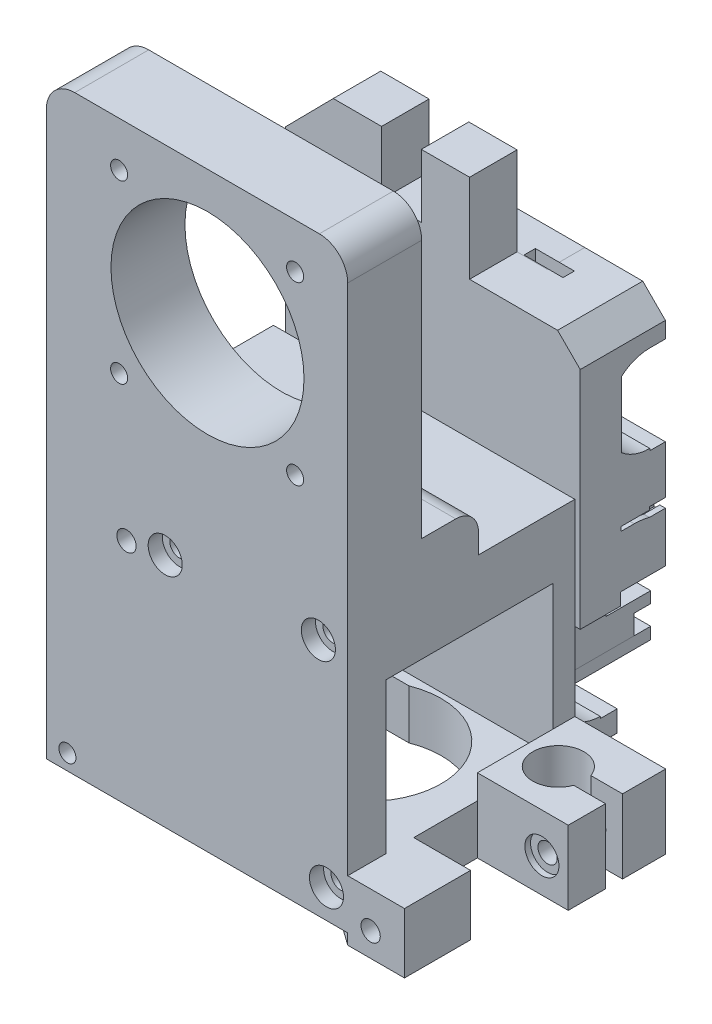
SolidWorks part; units mm, degrees
ref_plane "Front Plane" through (0, 0, 0) normal (0, 0, 1) x (1, 0, 0)
ref_plane "Top Plane" through (0, 0, 0) normal (0, 1, 0) x (1, 0, 0)
ref_plane "Right Plane" through (0, 0, 0) normal (1, 0, 0) x (0, 0, -1)
sketch "Sketch1" plane through (0, 0, 0) normal (0, 0, 1) x (1, 0, 0)
  line L1 (-22.5, 22.5) -> (22.5, 22.5)
  line L2 (-22.5, 22.5) -> (-22.5, -22.5)
  line L3 (-22.5, -22.5) -> (22.5, -22.5)
  line L4 (22.5, 22.5) -> (22.5, -22.5)
  line L5 (-22.5, 22.5) -> (22.5, -22.5) construction
  line L6 (-22.5, -22.5) -> (22.5, 22.5) construction
  point P0 (0, 0)
  dimension "D1" = 45
  dimension "D2" = 45
extrude "Boss-Extrude1" add sketch "Sketch1" along normal blind 35
sketch "Sketch2" plane through (0, 0, 35) normal (0, 0, 1) x (1, 0, 0)
  circle A0 centre (0, 0) radius 13
extrude "Cut-Extrude3" cut sketch "Sketch2" against normal blind 35
sketch "Sketch4" plane through (0, 0, 0) normal (0, 0, -1) x (-1, 0, 0)
  circle A0 centre (-15.8089, 15.9288) radius 1.7
sketch "Sketch5" plane through (0, 0, 0) normal (0, 0, -1) x (-1, 0, 0)
  circle A0 centre (-15.7813, -15.0653) radius 1.7
sketch "Sketch6" plane through (0, 0, 0) normal (0, 0, -1) x (-1, 0, 0)
  circle A0 centre (15.2203, -15.0657) radius 1.7
sketch "Sketch7" plane through (0, 0, 0) normal (0, 0, -1) x (-1, 0, 0)
  circle A0 centre (15.2, 15.9234) radius 1.7
extrude "Cut-Extrude8" cut sketch "Sketch4" against normal blind 35 contours A0
extrude "Cut-Extrude9" cut sketch "Sketch7" against normal blind 35 contours A0
extrude "Cut-Extrude10" cut sketch "Sketch6" against normal blind 35 contours A0
extrude "Cut-Extrude11" cut sketch "Sketch5" against normal blind 35 contours A0
sketch "Sketch8" plane through (22.5, 0, 0) normal (1, 0, 0) x (0, 0, -1)
  line L0 (-4.3639, -12.0361) -> (-35, -12.0361)
  line L2 (-35, -22.5) -> (-35, 22.5) construction
  line L3 (-35, -12.0361) -> (-35, 22.5)
  line L4 (-35, 22.5) -> (-8.4231, 22.5)
  line L5 (-35, 22.5) -> (0, 22.5) construction
  line L6 (-8.4231, 22.5) -> (-8.4231, 12.9255)
  line L7 (-8.4231, 12.9255) -> (-4.3639, 12.9255)
  line L8 (-4.3639, 12.9255) -> (-4.3639, -12.0361)
extrude "Cut-Extrude12" cut sketch "Sketch8" against normal blind 12
sketch "Sketch14" plane through (0, 22.5, 0) normal (0, 1, 0) x (1, 0, 0)
  line L1 (3.1909, -14.7293) -> (9.1909, -14.7293)
  line L2 (3.1909, -14.7293) -> (3.1909, -20.7293)
  line L3 (3.1909, -20.7293) -> (9.1909, -20.7293)
  line L4 (9.1909, -14.7293) -> (9.1909, -20.7293)
  line L5 (3.1909, -14.7293) -> (9.1909, -20.7293) construction
  line L6 (3.1909, -20.7293) -> (9.1909, -14.7293) construction
  point P0 (6.1909, -17.7293)
extrude "Boss-Extrude4" add sketch "Sketch14" along normal blind 2 and the other way blind 37.5
sketch "Sketch20" plane through (0, 24.5, 0) normal (0, 1, 0) x (1, 0, 0)
  line L0 (3.1909, -20.7293) -> (9.1909, -14.7293) construction
  circle A0 centre (6.1909, -17.7293) radius 2.2
  dimension "D1" = 4.4
extrude "Cut-Extrude17" cut sketch "Sketch20" against normal blind 7 and the other way through all contours A0
sketch "Sketch21" plane through (0, 17.5, 0) normal (0, 1, 0) x (1, 0, 0)
  circle A0 centre (6.1909, -17.7293) radius 1.75
extrude "Cut-Extrude18" cut sketch "Sketch21" against normal blind 2
ref_plane "Plane6" through (0, 16.5, 0) normal (0, 1, 0) x (1, 0, 0)
mirror "Mirror6" about plane through (0, 16.5, 0) normal (0, 1, 0) of "Cut-Extrude17"
sketch "Sketch22" plane through (0, -22.5, 0) normal (0, -1, 0) x (1, 0, 0)
  line L1 (-28.0826, 40.0025) -> (25, 40.0025)
  line L2 (-28.0826, 40.0025) -> (-28.0826, 0)
  line L3 (-28.0826, 0) -> (25, 0)
  line L4 (25, 40.0025) -> (25, 0)
  line L5 (-28.0826, 40.0025) -> (25, 0) construction
  line L6 (-28.0826, 0) -> (25, 40.0025) construction
  point P0 (-1.5413, 20.0013)
extrude "Boss-Extrude5" add sketch "Sketch22" along normal blind 44.5712 and the other way blind 1.5626
sketch "Sketch23" plane through (-28.0826, 0, 0) normal (-1, 0, 0) x (0, 0, 1)
  line L1 (3.8043, -58.359) -> (33.254, -58.359)
  line L2 (3.8043, -58.359) -> (3.8043, -31.8415)
  line L3 (3.8043, -31.8415) -> (33.254, -31.8415)
  line L4 (33.254, -58.359) -> (33.254, -31.8415)
  line L5 (3.8043, -58.359) -> (33.254, -31.8415) construction
  line L6 (3.8043, -31.8415) -> (33.254, -58.359) construction
  point P0 (18.5291, -45.1003)
extrude "Cut-Extrude19" cut sketch "Sketch23" against normal through all
sketch "Sketch25" plane through (0, -20.9374, 0) normal (0, 1, 0) x (1, 0, 0)
  circle A0 centre (6.1909, -17.7293) radius 5
extrude "Cut-Extrude24" cut sketch "Sketch25" against normal blind 2.6
sketch "Sketch26" plane through (0, -23.5374, 0) normal (0, 1, 0) x (1, 0, 0)
  circle A0 centre (6.1909, -17.7293) radius 8.1
extrude "Cut-Extrude25" cut sketch "Sketch26" against normal blind 4 contours A0
sketch "Sketch27" plane through (0, -27.5374, 0) normal (0, 1, 0) x (1, 0, 0)
  circle A0 centre (6.1909, -17.7293) radius 6.7
extrude "Cut-Extrude28" cut sketch "Sketch27" against normal blind 6
sketch "Sketch30" plane through (0, -58.359, 0) normal (0, 1, 0) x (1, 0, 0)
  circle A0 centre (6.2079, -17.7293) radius 13
extrude "Cut-Extrude30" cut sketch "Sketch30" against normal blind 10.7676
sketch "Sketch31" plane through (0, -67.0712, 0) normal (0, -1, 0) x (1, 0, 0)
  line L1 (-17.2669, 29.2843) -> (2.0826, 29.2843)
  line L2 (-17.2669, 29.2843) -> (-17.2669, 5.6402)
  line L3 (-17.2669, 5.6402) -> (2.0826, 5.6402)
  line L4 (2.0826, 29.2843) -> (2.0826, 5.6402)
  line L5 (-17.2669, 29.2843) -> (2.0826, 5.6402) construction
  line L6 (-17.2669, 5.6402) -> (2.0826, 29.2843) construction
  point P0 (-7.5922, 17.4622)
extrude "Cut-Extrude31" cut sketch "Sketch31" against normal blind 9.6643
sketch "Sketch34" plane through (-28.0826, 0, 0) normal (-1, 0, 0) x (0, 0, 1)
  circle A4 centre (35.5309, -28.495) radius 1.5
  circle A5 centre (3.5309, -28.495) radius 1.5
  circle A6 centre (35.5309, -60.495) radius 1.5
  circle A7 centre (3.5309, -60.495) radius 1.5
extrude "Cut-Extrude32" cut sketch "Sketch34" against normal blind 9 contours A5 | A7 | A6 | A4
sketch "Sketch37" plane through (25, 0, 0) normal (1, 0, 0) x (0, 0, -1)
  line L1 (-28.3675, -68.9589) -> (-40.0025, -68.9589)
  line L2 (-28.3675, -68.9589) -> (-28.3675, -58.359)
  line L3 (-28.3675, -58.359) -> (-40.0025, -58.359)
  line L4 (-40.0025, -68.9589) -> (-40.0025, -58.359)
  line L5 (-28.3675, -68.9589) -> (-40.0025, -58.359) construction
  line L6 (-28.3675, -58.359) -> (-40.0025, -68.9589) construction
  point P0 (-34.185, -63.659)
extrude "Boss-Extrude6" add sketch "Sketch37" along normal blind 10 and the other way blind 5 draft 29
sketch "Sketch38" plane through (0, 0, 40.0025) normal (0, 0, 1) x (1, 0, 0)
  circle A0 centre (29.0349, -64.7484) radius 1.7
extrude "Cut-Extrude33" cut sketch "Sketch38" against normal blind 10 contours A0
sketch "Sketch39" plane through (0, 0, 40.0025) normal (0, 0, 1) x (1, 0, 0)
  circle A0 centre (-13.9651, -26.7484) radius 1.7
extrude "Cut-Extrude34" cut sketch "Sketch39" against normal through all contours A0
sketch "Sketch40" plane through (25, 0, 0) normal (1, 0, 0) x (0, 0, -1)
  line L0 (0, -67.0712) -> (-28.3675, -67.0712) construction
  line L1 (-17.1599, -54.0712) -> (0, -54.0712)
  line L2 (-17.1599, -54.0712) -> (-17.1599, -67.0712)
  line L3 (-17.1599, -67.0712) -> (0, -67.0712)
  line L4 (0, -54.0712) -> (0, -67.0712)
  line L5 (-17.1599, -54.0712) -> (0, -67.0712) construction
  line L6 (-17.1599, -67.0712) -> (0, -54.0712) construction
  point P0 (-8.5799, -60.5712)
extrude "Boss-Extrude7" add sketch "Sketch40" along normal blind 16 contours L2 L3 L4 L1
sketch "Sketch41" plane through (0, -54.0712, 1.2693) normal (0, 1, 0) x (1, 0, 0)
  circle A0 centre (31.1639, -7.7934) radius 4.5
extrude "Cut-Extrude35" cut sketch "Sketch41" against normal blind 15 contours A0
sketch "Sketch42" plane through (0, -54.0712, 0) normal (0, 1, 0) x (1, 0, 0)
  line L1 (33.5282, -7.5957) -> (42.8596, -7.5957)
  line L2 (33.5282, -7.5957) -> (33.5282, -10.5957)
  line L3 (33.5282, -10.5957) -> (42.8596, -10.5957)
  line L4 (42.8596, -7.5957) -> (42.8596, -10.5957)
  line L5 (33.5282, -7.5957) -> (42.8596, -10.5957) construction
  line L6 (33.5282, -10.5957) -> (42.8596, -7.5957) construction
  point P0 (38.1939, -9.0957)
extrude "Cut-Extrude36" cut sketch "Sketch42" against normal blind 15
sketch "Sketch43" plane through (0, 0, 0) normal (0, 0, -1) x (-1, 0, 0)
  line L1 (-34.6289, -64.4039) -> (-32.7385, -61.0954)
  line L2 (-32.7385, -61.0954) -> (-34.6585, -57.804)
  line L3 (-34.6585, -57.804) -> (-38.4689, -57.821)
  line L4 (-38.4689, -57.821) -> (-40.3594, -61.1295)
  line L5 (-40.3594, -61.1295) -> (-38.4394, -64.421)
  line L6 (-38.4394, -64.421) -> (-34.6289, -64.4039)
  circle A1 centre (-36.5489, -61.1125) radius 3.3 construction
extrude "Cut-Extrude37" cut sketch "Sketch43" against normal blind 5
sketch "Sketch44" plane through (0, 0, 17.1599) normal (0, 0, 1) x (1, 0, 0)
  circle A0 centre (36.3605, -61.0871) radius 1.7
extrude "Cut-Extrude38" cut sketch "Sketch44" against normal blind 23 contours A0
sketch "Sketch48" plane through (0, 0, 0) normal (0, 0, -1) x (-1, 0, 0)
  line L1 (9.0667, -28.8111) -> (10.9572, -25.5026)
  line L2 (10.9572, -25.5026) -> (9.0372, -22.2111)
  line L3 (9.0372, -22.2111) -> (5.2267, -22.2282)
  line L4 (5.2267, -22.2282) -> (3.3362, -25.5367)
  line L5 (3.3362, -25.5367) -> (5.2563, -28.8281)
  line L6 (5.2563, -28.8281) -> (9.0667, -28.8111)
  circle A1 centre (7.1467, -25.5196) radius 3.3 construction
sketch "Sketch49" plane through (0, 0, 0) normal (0, 0, -1) x (-1, 0, 0)
  line L1 (-19.3395, -65.2659) -> (-17.449, -61.9575)
  line L2 (-17.449, -61.9575) -> (-19.369, -58.666)
  line L3 (-19.369, -58.666) -> (-23.1795, -58.6831)
  line L4 (-23.1795, -58.6831) -> (-25.07, -61.9916)
  line L5 (-25.07, -61.9916) -> (-23.15, -65.283)
  line L6 (-23.15, -65.283) -> (-19.3395, -65.2659)
  circle A1 centre (-21.2595, -61.9745) radius 3.3 construction
sketch "Sketch50" plane through (0, 0, 0) normal (0, 0, -1) x (-1, 0, 0)
  line L1 (-17.9116, -28.2435) -> (-16.0212, -24.935)
  line L2 (-16.0212, -24.935) -> (-17.9412, -21.6436)
  line L3 (-17.9412, -21.6436) -> (-21.7517, -21.6606)
  line L4 (-21.7517, -21.6606) -> (-23.6421, -24.9691)
  line L5 (-23.6421, -24.9691) -> (-21.7221, -28.2606)
  line L6 (-21.7221, -28.2606) -> (-17.9116, -28.2435)
  circle A1 centre (-19.8316, -24.9521) radius 3.3 construction
sketch "Sketch51" plane through (0, 0, 40.0025) normal (0, 0, 1) x (1, 0, 0)
  circle A0 centre (-7.1467, -25.5196) radius 1.7
sketch "Sketch52" plane through (0, 0, 40.0025) normal (0, 0, 1) x (1, 0, 0)
  circle A0 centre (19.8316, -24.9521) radius 1.7
sketch "Sketch53" plane through (0, 0, 40.0025) normal (0, 0, 1) x (1, 0, 0)
  circle A0 centre (21.2595, -61.9745) radius 1.7
extrude "Cut-Extrude39" cut sketch "Sketch48" against normal blind 5
extrude "Cut-Extrude40" cut sketch "Sketch49" against normal blind 5
extrude "Cut-Extrude41" cut sketch "Sketch50" against normal blind 5
extrude "Cut-Extrude42" cut sketch "Sketch53" against normal through all contours A0
extrude "Cut-Extrude43" cut sketch "Sketch52" against normal through all contours A0
extrude "Cut-Extrude44" cut sketch "Sketch51" against normal through all
sketch "Sketch55" plane through (0, 0, 0) normal (0, 0, -1) x (-1, 0, 0)
  line L1 (16.7453, -30.1645) -> (18.3136, -26.0487)
  line L2 (18.3136, -26.0487) -> (15.5334, -22.6326)
  line L3 (15.5334, -22.6326) -> (11.1849, -23.3323)
  line L4 (11.1849, -23.3323) -> (9.6166, -27.448)
  line L5 (9.6166, -27.448) -> (12.3967, -30.8642)
  line L6 (12.3967, -30.8642) -> (16.7453, -30.1645)
  circle A0 centre (13.9651, -26.7484) radius 3.8144 construction
extrude "Cut-Extrude46" cut sketch "Sketch55" against normal blind 5
sketch "Sketch57" plane through (0, 0, 40.0025) normal (0, 0, 1) x (1, 0, 0)
  circle A0 centre (-7.1467, -25.5196) radius 3
sketch "Sketch58" plane through (0, 0, 40.0025) normal (0, 0, 1) x (1, 0, 0)
  circle A0 centre (19.8316, -24.9521) radius 3
sketch "Sketch59" plane through (0, 0, 40.0025) normal (0, 0, 1) x (1, 0, 0)
  circle A0 centre (21.2595, -61.9745) radius 3
extrude "Cut-Extrude48" cut sketch "Sketch57" against normal blind 2.5
extrude "Cut-Extrude49" cut sketch "Sketch58" against normal blind 2.5 contours A0
extrude "Cut-Extrude50" cut sketch "Sketch59" against normal blind 2.5 contours A0
sketch "Sketch60" plane through (0, 0, 0) normal (0, 0, -1) x (-1, 0, 0)
  circle A0 centre (-15.8089, 15.9288) radius 3
  circle A1 centre (15.2, 15.9234) radius 3
  circle A2 centre (-15.7813, -15.0653) radius 3
  circle A3 centre (15.2203, -15.0657) radius 3
extrude "Cut-Extrude51" cut sketch "Sketch60" against normal blind 1
sketch "Sketch61" plane through (9.1909, 0, 0) normal (1, 0, 0) x (0, 0, -1)
  line L1 (-21.0836, 7.2178) -> (-14.5415, 7.2178)
  line L2 (-21.0836, 7.2178) -> (-21.0836, -6.8125)
  line L3 (-21.0836, -6.8125) -> (-14.5415, -6.8125)
  line L4 (-14.5415, 7.2178) -> (-14.5415, -6.8125)
  line L5 (-21.0836, 7.2178) -> (-14.5415, -6.8125) construction
  line L6 (-21.0836, -6.8125) -> (-14.5415, 7.2178) construction
  point P0 (-17.8126, 0.2026)
extrude "Cut-Extrude52" cut sketch "Sketch61" against normal blind 6.5 contours L3 L4 L1 L2
sketch "Sketch62" plane through (-22.5, 0, 0) normal (-1, 0, 0) x (0, 0, 1)
  circle A0 centre (9.4038, -7.1271) radius 1.7
sketch "Sketch63" plane through (-22.5, 0, 0) normal (-1, 0, 0) x (0, 0, 1)
  circle A0 centre (29.5162, -7.0688) radius 1.7
sketch "Sketch67" plane through (-22.5, -2.4684, 0) normal (-1, 0, 0) x (0, 0, 1)
  line L1 (26.7141, -1.4425) -> (32.3183, -1.4425)
  line L2 (26.7141, -1.4425) -> (26.7141, -10.4391)
  line L3 (26.7141, -10.4391) -> (32.3183, -10.4391)
  line L4 (32.3183, -1.4425) -> (32.3183, -10.4391)
  line L5 (26.7141, -1.4425) -> (32.3183, -10.4391) construction
  line L6 (26.7141, -10.4391) -> (32.3183, -1.4425) construction
  point P0 (29.5162, -5.9408)
extrude "Boss-Extrude8" add sketch "Sketch67" against normal blind 33
sketch "Sketch68" plane through (-22.5, -2.4684, 0) normal (-1, 0, 0) x (0, 0, 1)
  line L1 (6.6705, -1.2663) -> (12.2748, -1.2663)
  line L2 (6.6705, -1.2663) -> (6.6705, -10.6664)
  line L3 (6.6705, -10.6664) -> (12.2748, -10.6664)
  line L4 (12.2748, -1.2663) -> (12.2748, -10.6664)
  line L5 (6.6705, -1.2663) -> (12.2748, -10.6664) construction
  line L6 (6.6705, -10.6664) -> (12.2748, -1.2663) construction
  point P0 (9.4726, -5.9663)
extrude "Boss-Extrude9" add sketch "Sketch68" against normal blind 33
extrude "Cut-Extrude55" cut sketch "Sketch63" against normal through all contours A0
extrude "Cut-Extrude56" cut sketch "Sketch62" against normal through all contours A0
sketch "Sketch69" plane through (-22.5, 0, 0) normal (-1, 0, 0) x (0, 0, 1)
  circle A0 centre (9.4038, -7.1271) radius 3
  circle A1 centre (29.5162, -7.0688) radius 3
extrude "Cut-Extrude57" cut sketch "Sketch69" against normal blind 2.5
sketch "Sketch70" plane through (0, 0, 28.3675) normal (0, 0, -1) x (-1, 0, 0)
  line L1 (-25.0573, -66.8115) -> (-25.2594, -62.3352)
  line L2 (-25.2594, -62.3352) -> (-29.2371, -60.2722)
  line L3 (-29.2371, -60.2722) -> (-33.0125, -62.6853)
  line L4 (-33.0125, -62.6853) -> (-32.8104, -67.1616)
  line L5 (-32.8104, -67.1616) -> (-28.8328, -69.2246)
  line L6 (-28.8328, -69.2246) -> (-25.0573, -66.8115)
  circle A0 centre (-29.0349, -64.7484) radius 3.8805 construction
extrude "Cut-Extrude58" cut sketch "Sketch70" against normal blind 2.5
sketch "Sketch71" plane through (0, 0, 17.1599) normal (0, 0, 1) x (1, 0, 0)
  circle A0 centre (36.3605, -61.0871) radius 3
extrude "Cut-Extrude59" cut sketch "Sketch71" against normal blind 1 contours A0
sketch "Sketch73" plane through (0, 0, 40.0025) normal (0, 0, 1) x (1, 0, 0)
  circle A0 centre (-24.3693, -64.3228) radius 1.5
extrude "Cut-Extrude61" cut sketch "Sketch73" against normal blind 5
ref_plane "Plane7" through (0, 0, 17.7293) normal (0, 0, 1) x (1, 0, 0)
ref_plane "Plane8" through (0, -20.9374, 0) normal (0, 1, 0) x (1, 0, 0)
sketch "Sketch78" plane through (0, 0, 17.7293) normal (0, 0, 1) x (1, 0, 0)
  line L0 (25, -20.9374) -> (-28.0826, -20.9374) construction
  line L1 (-33.1226, -20.9374) -> (49.9762, -20.9374)
  line L2 (-33.1226, -20.9374) -> (-33.1226, -72.7681)
  line L3 (-33.1226, -72.7681) -> (49.9762, -72.7681)
  line L4 (49.9762, -20.9374) -> (49.9762, -72.7681)
sketch "Sketch79" plane through (0, -20.9374, 0) normal (0, 1, 0) x (1, 0, 0)
  line L1 (-52.1, -49.3859) -> (43.5589, -49.3859)
  line L2 (-52.1, -49.3859) -> (-52.1, 1.9049)
  line L3 (-52.1, 1.9049) -> (43.5589, 1.9049)
  line L4 (43.5589, -49.3859) -> (43.5589, 1.9049)
extrude "Cut-Extrude62" cut sketch "Sketch79" along normal blind 59 contours L1 L4 L3 L2
sketch "Sketch80" plane through (0, -20.9374, 0) normal (0, 1, 0) x (1, 0, 0)
  line L1 (25, -40.0025) -> (-28.0826, -40.0025)
  line L2 (25, -40.0025) -> (25, -26.9707)
  line L3 (25, -26.9707) -> (-28.0826, -26.9707)
  line L4 (-28.0826, -40.0025) -> (-28.0826, -26.9707)
  line L5 (25, -40.0025) -> (-28.0826, -26.9707) construction
  line L6 (25, -26.9707) -> (-28.0826, -40.0025) construction
  line L7 (25, 0) -> (25, -40.0025) construction
  line L8 (-28.0826, -40.0025) -> (-28.0826, 0) construction
  line L9 (25, -40.0025) -> (-28.0826, -40.0025) construction
  point P0 (-1.5413, -33.4866)
extrude "Boss-Extrude10" add sketch "Sketch80" along normal blind 58
fillet "Fillet1" radius 5 2 edges at (-28.0826, 37.0626, 33.4866) (25, 37.0626, 33.4866)
sketch "Sketch84" plane through (0, 0, 26.9707) normal (0, 0, -1) x (-1, 0, 0)
  circle A0 centre (-0.299, 13.6036) radius 17
extrude "Cut-Extrude63" cut sketch "Sketch84" against normal blind 22
sketch "Sketch85" plane through (0, 0, 40.0025) normal (0, 0, 1) x (1, 0, 0)
  circle A0 centre (15.7368, 29.1356) radius 1.5
  circle A1 centre (15.7368, -1.8644) radius 1.5
  circle A2 centre (-15.2632, -1.8644) radius 1.5
  circle A3 centre (-15.2632, 29.1356) radius 1.5
extrude "Cut-Extrude64" cut sketch "Sketch85" against normal blind 15
sketch "Sketch86" plane through (0, -20.9374, 0) normal (0, 1, 0) x (1, 0, 0)
  line L0 (25, -26.9707) -> (-28.0826, -26.9707) construction
  line L1 (-28.0826, -26.9707) -> (-14.3865, -26.9707)
  line L2 (-28.0826, -26.9707) -> (-28.0826, -16.9707)
  line L3 (-28.0826, -16.9707) -> (-14.3865, -16.9707)
  line L4 (-14.3865, -26.9707) -> (-14.3865, -16.9707)
extrude "Boss-Extrude11" add sketch "Sketch86" along normal blind 7.5
fillet "Fillet3" radius 3 1 edges at (-21.2346, -13.4374, 16.9707)
sketch "Sketch87" plane through (0, -20.9374, 0) normal (0, 1, 0) x (1, 0, 0)
  line L0 (25, -26.9707) -> (-14.3865, -26.9707) construction
  line L1 (25, -16.9707) -> (14.2343, -16.9707)
  line L2 (25, -16.9707) -> (25, -26.9707)
  line L3 (25, -26.9707) -> (14.2343, -26.9707)
  line L4 (14.2343, -16.9707) -> (14.2343, -26.9707)
  line L5 (-14.3865, -16.9707) -> (-28.0826, -16.9707) construction
  line L6 (25, 0) -> (25, -26.9707) construction
extrude "Boss-Extrude12" add sketch "Sketch87" along normal blind 7.5
sketch "Sketch89" plane through (0, -20.9374, 0) normal (0, 1, 0) x (1, 0, 0)
  line L1 (61.8406, -52.5891) -> (-70.6943, -52.5891)
  line L2 (61.8406, -52.5891) -> (61.8406, 20.0544)
  line L3 (61.8406, 20.0544) -> (-70.6943, 20.0544)
  line L4 (-70.6943, -52.5891) -> (-70.6943, 20.0544)
fillet "Fillet6" radius 4 1 edges at (19.6171, -13.4374, 16.9707)
sketch "Sketch90" plane through (0, 0, 0) normal (0, 0, -1) x (-1, 0, 0)
  line L0 (17.0373, -68.362) -> (17.0373, -50.6891)
  line L1 (14.2497, -71.1901) -> (-14.1775, -71.1901)
  line L2 (25.9937, -36.474) -> (25.9937, 10.3734)
  line L4 (-25.9551, -36.6603) -> (-25.9551, -0.6679)
  line L5 (17.0373, -50.6891) -> (26.0173, -50.6891)
  line L6 (-17.4627, -50.6803) -> (-17.4627, -67.8636)
  line L7 (-17.4627, -50.6803) -> (-23.3678, -50.6803)
  line L8 (-17.4627, -67.8636) -> (-14.1775, -71.1901)
  line L9 (17.0373, -68.362) -> (14.2497, -71.1901)
  line L10 (-23.3678, -50.6803) -> (-23.3627, -48.6193)
  line L11 (-23.3627, -43.1803) -> (-23.3627, -48.6193)
  line L13 (26.0173, -50.6891) -> (26.0173, -40.6819)
  line L14 (26.0173, -40.6819) -> (25.9937, -36.474)
  line L15 (-25.9551, -0.6679) -> (-21.9627, 3.3244)
  line L16 (-21.9627, 3.3244) -> (-6.4627, 3.3557)
  line L17 (-6.4627, 3.3557) -> (-6.4627, 18.9227)
  line L18 (-23.3627, -43.1803) -> (-23.3627, -40.3081)
  line L19 (17.549, 18.9227) -> (25.9937, 10.3734)
  line L20 (2.0414, 18.9227) -> (2.0108, 7.7806)
  line L21 (9.0396, 7.7806) -> (9.0396, 18.9227)
  line L22 (2.0108, 7.7806) -> (9.0396, 7.7806)
  line L23 (2.0414, 18.9227) -> (-6.4627, 18.9227)
  line L24 (9.0396, 18.9227) -> (17.549, 18.9227)
  line L25 (-25.9551, -36.6603) -> (-25.9551, -40.3081)
  line L26 (-25.9551, -40.3081) -> (-23.3627, -40.3081)
extrude "Boss-Extrude13" add sketch "Sketch90" along normal blind 15
ref_plane "Plane9" through (24.9551, 0, 0) normal (1, 0, 0) x (0, 0, -1)
sketch "Sketch93" plane through (24.9551, 0, 0) normal (1, 0, 0) x (0, 0, -1)
  circle A0 centre (12.2562, -11.1714) radius 7.6272
extrude "Cut-Extrude66" cut sketch "Sketch93" against normal blind 49.5
sketch "Sketch94" plane through (25.9551, 0, 0) normal (1, 0, 0) x (0, 0, -1)
  line L0 (7.3045, -5.318) -> (7.3045, -17.0156)
  line L1 (12.2545, -3.5044) -> (16.3704, -3.5044)
  line L2 (16.3704, -4.7037) -> (16.3704, -3.5044)
  line L3 (12.2545, -18.8291) -> (12.2475, -19.1753)
  line L4 (12.2475, -19.1753) -> (15.2475, -19.1908)
  line L5 (15.2475, -19.1908) -> (15.2475, -18.2204)
  arc A0 (7.3045, -17.0156) -> (12.2545, -18.8291) centre (12.2545, -11.1668) ccw
  arc A1 (12.2545, -3.5044) -> (7.3045, -5.318) centre (12.2545, -11.1668) ccw
  arc A2 (15.2475, -18.2204) -> (16.3704, -4.7037) centre (12.2545, -11.1668) ccw
extrude "Cut-Extrude67" cut sketch "Sketch94" against normal blind 53.5
ref_plane "Plane10" through (12.4627, 0, 0) normal (1, 0, 0) x (0, 0, -1)
sketch "Sketch95" plane through (12.4627, 0, 0) normal (1, 0, 0) x (0, 0, -1)
  circle A0 centre (12.0924, -56.1751) radius 7.6764
extrude "Cut-Extrude68" cut sketch "Sketch95" against normal blind 25.2
sketch "Sketch96" plane through (17.4627, 0, 0) normal (1, 0, 0) x (0, 0, -1)
  line L0 (7.0266, -61.9445) -> (7.0939, -50.6803)
  line L1 (7.0939, -50.6803) -> (18.0396, -50.6803)
  line L3 (12.0174, -63.8278) -> (12.0174, -64.1642)
  line L4 (12.0174, -64.1642) -> (15, -64.1642)
  line L5 (15, -50.6803) -> (15, -67.8636) construction
  line L6 (15, -64.1642) -> (15, -63.2948)
  arc A0 (7.0266, -61.9445) -> (12.0174, -63.8278) centre (12.1456, -55.9335) ccw
  arc A1 (15, -63.2948) -> (18.0396, -50.6803) centre (12.1456, -55.9335) ccw
extrude "Cut-Extrude69" cut sketch "Sketch96" against normal blind 34.5
sketch "Sketch98" plane through (23.3627, 0, 0) normal (1, 0, 0) x (0, 0, -1)
  line L1 (7.1104, -43.1905) -> (15.1235, -43.1905)
  line L2 (7.1104, -43.1905) -> (7.1104, -38.1356)
  line L3 (7.1104, -38.1356) -> (15.1235, -38.1356)
  line L4 (15.1235, -43.1905) -> (15.1235, -38.1356)
extrude "Cut-Extrude70" cut sketch "Sketch98" against normal through all both and the other way through all
sketch "Sketch99" plane through (23.3627, 0, 0) normal (1, 0, 0) x (0, 0, -1)
  line L1 (15, -48.6193) -> (12.1018, -48.6193)
  line L2 (15, -48.6193) -> (15, -45.1749)
  line L3 (15, -45.1749) -> (12.1018, -45.1749)
  line L4 (12.1018, -48.6193) -> (12.1018, -45.1749)
extrude "Cut-Extrude71" cut sketch "Sketch99" against normal blind 49.5
sketch "Sketch100" plane through (0, 0, -15) normal (0, 0, -1) x (-1, 0, 0)
  line L0 (-25.9551, -28.9452) -> (-24.9628, -28.9452)
  line L1 (-25.9551, -19.1895) -> (-25.9551, -38.1356) construction
  line L2 (-24.9628, -28.9452) -> (-24.9628, -29.6536)
  line L3 (-24.9628, -29.6536) -> (-23.9626, -29.6536)
  line L4 (-23.9626, -29.6536) -> (-23.9626, -28.9452)
  line L5 (-23.9626, -28.9452) -> (-22.9642, -28.9452)
  line L6 (-22.9642, -28.9452) -> (-22.9586, -29.6536)
  line L7 (-22.9586, -29.6536) -> (-21.963, -29.6536)
  line L8 (-21.963, -29.6536) -> (-21.963, -28.9452)
  line L9 (-21.963, -28.9452) -> (-20.9649, -28.9452)
  line L10 (-20.9649, -28.9452) -> (-20.9593, -29.6526)
  line L11 (-20.9593, -29.6526) -> (-19.966, -29.6447)
  line L12 (-19.966, -29.6447) -> (-19.9723, -28.852)
  line L13 (-19.9723, -28.852) -> (-19.3112, -28.5436)
  line L14 (-19.3112, -28.5436) -> (-19.0086, -29.1925)
  line L15 (-19.0086, -29.1925) -> (-18.1014, -28.7694)
  line L16 (-18.1014, -28.7694) -> (-18.4041, -28.1205)
  line L17 (-18.4041, -28.1205) -> (-17.5043, -27.7008)
  line L18 (-17.5043, -27.7008) -> (-17.2016, -28.3497)
  line L19 (-17.2016, -28.3497) -> (-16.2902, -27.9246)
  line L20 (-16.2902, -27.9246) -> (-16.5928, -27.2757)
  line L21 (-16.5928, -27.2757) -> (-15.6945, -26.8567)
  line L22 (-15.6945, -26.8567) -> (-15.2198, -27.8743)
  line L23 (-15.2198, -27.8743) -> (-14.3102, -27.4501)
  line L24 (-14.3102, -27.4501) -> (-14.7283, -26.5536)
  line L25 (-14.7283, -26.5536) -> (-13.7535, -26.5536)
  line L26 (-13.7535, -26.5536) -> (-13.7535, -27.2739)
  line L27 (-13.7535, -27.2739) -> (-12.7588, -27.2739)
  line L28 (-12.7588, -27.2739) -> (-12.7588, -26.5536)
  line L29 (-12.7588, -26.5536) -> (-11.7545, -26.5536)
  line L30 (-11.7545, -26.5536) -> (-11.7545, -27.2739)
  line L31 (-11.7545, -27.2739) -> (-10.7569, -27.2739)
  line L32 (-10.7569, -27.2739) -> (-10.7569, -26.5536)
  line L33 (-10.7569, -26.5536) -> (-9.7531, -26.5536)
  line L34 (-9.7531, -26.5536) -> (-9.7531, -27.2739)
  line L35 (-9.7531, -27.2739) -> (-8.7561, -27.2739)
  line L36 (-8.7561, -27.2739) -> (-8.7561, -26.5536)
  line L37 (-8.7561, -26.5536) -> (-7.7518, -26.5536)
  line L38 (-7.7518, -26.5536) -> (-7.7518, -27.2739)
  line L39 (-7.7518, -27.2739) -> (-7.4588, -27.2739)
  line L40 (-7.4588, -27.2739) -> (-6.7129, -27.7765)
  line L41 (-6.7129, -27.7765) -> (-6.455, -27.9003)
  line L42 (-6.455, -27.9003) -> (-6.8083, -25.7675)
  line L43 (-6.8083, -25.7675) -> (-15.08, -25.7675)
  line L44 (-15.08, -25.7675) -> (-20.1972, -28.16)
  line L45 (-20.1972, -28.16) -> (-25.9551, -28.1993)
  line L46 (-25.9551, -28.1993) -> (-25.9551, -28.9452)
sketch "Sketch104" plane through (0, 0, -15) normal (0, 0, -1) x (-1, 0, 0)
  line L0 (-25.9627, -29.3147) -> (-24.9628, -29.3147)
  line L1 (-24.9628, -28.9452) -> (-24.9628, -29.6536) construction
  line L2 (-24.9628, -29.3147) -> (-24.9627, -30.0666)
  line L3 (-24.9627, -30.0666) -> (-23.9627, -30.0666)
  line L4 (-23.9627, -30.0666) -> (-23.9626, -29.2994)
  line L5 (-23.9626, -29.6536) -> (-23.9626, -28.9452) construction
  line L6 (-23.9626, -29.2994) -> (-22.9614, -29.2994)
  line L7 (-22.9642, -28.9452) -> (-22.9586, -29.6536) construction
  line L8 (-22.9614, -29.2994) -> (-22.9627, -30.0666)
  line L9 (-22.9627, -30.0666) -> (-21.9627, -30.0666)
  line L10 (-21.9627, -30.0666) -> (-21.9627, -29.3147)
  line L11 (-21.9627, -29.3147) -> (-20.9627, -29.3147)
  line L12 (-20.9627, -29.3147) -> (-20.9627, -30.0666)
  line L13 (-20.9627, -30.0666) -> (-19.9627, -30.0666)
  line L14 (-19.9627, -30.0666) -> (-19.9627, -29.3)
  line L15 (-19.9627, -29.3) -> (-19.1441, -28.9183)
  line L16 (-19.1441, -28.9183) -> (-18.8263, -29.5997)
  line L17 (-18.8263, -29.5997) -> (-17.92, -29.1771)
  line L18 (-17.92, -29.1771) -> (-18.2378, -28.4956)
  line L19 (-18.2378, -28.4956) -> (-17.3315, -28.073)
  line L20 (-17.3315, -28.073) -> (-17.0137, -28.7545)
  line L21 (-17.0137, -28.7545) -> (-16.1074, -28.3318)
  line L22 (-16.1074, -28.3318) -> (-16.4252, -27.6504)
  line L23 (-16.4252, -27.6504) -> (-15.5188, -27.2278)
  line L24 (-15.5188, -27.2278) -> (-15.2011, -27.9092)
  line L25 (-15.2011, -27.9092) -> (-14.2948, -27.4866)
  line L26 (-14.2948, -27.4866) -> (-14.5521, -26.9347)
  line L27 (-14.5521, -26.9347) -> (-13.7627, -26.9347)
  line L28 (-13.7627, -26.9347) -> (-13.7627, -27.6866)
  line L29 (-13.7627, -27.6866) -> (-12.7627, -27.6866)
  line L30 (-12.7627, -27.6866) -> (-12.7588, -26.9137)
  line L31 (-12.7588, -27.2739) -> (-12.7588, -26.5536) construction
  line L32 (-12.7588, -26.9137) -> (-11.7627, -26.9347)
  line L33 (-11.7627, -26.9347) -> (-11.7627, -27.6866)
  line L34 (-11.7627, -27.6866) -> (-10.7627, -27.6866)
  line L35 (-10.7627, -27.6866) -> (-10.7627, -26.9347)
  line L36 (-10.7627, -26.9347) -> (-9.7627, -26.9347)
  line L37 (-9.7627, -26.9347) -> (-9.7627, -27.6866)
  line L38 (-9.7627, -27.6866) -> (-8.7627, -27.6866)
  line L39 (-8.7627, -27.6866) -> (-8.7627, -26.9347)
  line L40 (-8.7627, -26.9347) -> (-7.7627, -26.9347)
  line L41 (-7.7627, -26.9347) -> (-7.7627, -27.6866)
  line L42 (-7.7627, -27.6866) -> (-6.8547, -27.6866)
  line L43 (-6.8547, -27.6866) -> (-6.8367, -25.2817)
  line L44 (-6.8367, -25.2817) -> (-6.8381, -25.2833)
  line L45 (-6.8381, -25.2833) -> (-15.2958, -25.3392)
  line L46 (-15.2958, -25.3392) -> (-20.3315, -27.6866)
  line L47 (-20.3315, -27.6866) -> (-25.9551, -27.6866)
  line L48 (-25.9551, -19.1895) -> (-25.9551, -38.1356) construction
  line L49 (-25.9551, -27.6866) -> (-25.9627, -29.3147)
extrude "Cut-Extrude75" cut sketch "Sketch104" against normal blind 2.8
extrude "Cut-Extrude76" cut sketch "Sketch100" against normal blind 7.8
ref_plane "Plane11" through (25.9551, -29.3147, -12.2) normal (-1, 0, 0) x (0, 0, 1)
fillet "Fillet9" radius 10 1 edges at (25.4589, -28.9452, -12.2)
sketch "Sketch107" plane through (0, 0, -15) normal (0, 0, -1) x (-1, 0, 0)
  line L0 (8.6873, -27.1166) -> (8.6873, -26.3647)
  line L1 (8.6873, -26.3647) -> (9.6873, -26.3647)
  line L2 (9.6873, -26.3647) -> (9.6873, -27.1166)
  line L3 (9.6873, -27.1166) -> (10.6873, -27.1166)
  line L4 (10.6873, -27.1166) -> (10.6873, -26.3647)
  line L5 (10.6873, -26.3647) -> (11.3006, -26.3647)
  line L6 (11.3006, -26.3647) -> (11.5044, -26.4824)
  line L7 (11.5044, -26.4824) -> (11.1285, -27.1335)
  line L8 (11.1285, -27.1335) -> (11.9945, -27.6335)
  line L9 (11.9945, -27.6335) -> (12.3705, -26.9824)
  line L10 (12.3705, -26.9824) -> (13.2365, -27.4824)
  line L11 (13.2365, -27.4824) -> (12.8606, -28.1335)
  line L12 (12.8606, -28.1335) -> (13.7266, -28.6335)
  line L13 (13.7266, -28.6335) -> (14.1025, -27.9824)
  line L14 (14.1025, -27.9824) -> (14.9685, -28.4824)
  line L15 (14.9685, -28.4824) -> (14.5926, -29.1335)
  line L16 (14.5926, -29.1335) -> (15.4586, -29.6335)
  line L17 (15.4586, -29.6335) -> (15.8346, -28.9824)
  line L18 (15.8346, -28.9824) -> (16.7006, -29.4824)
  line L19 (16.7006, -29.4824) -> (16.3247, -30.1335)
  line L20 (16.3247, -30.1335) -> (17.1907, -30.6335)
  line L21 (17.1907, -30.6335) -> (17.5666, -29.9824)
  line L22 (17.5666, -29.9824) -> (18.4326, -30.4824)
  line L23 (18.4326, -30.4824) -> (18.0567, -31.1335)
  line L24 (18.0567, -31.1335) -> (18.9227, -31.6335)
  line L25 (18.9227, -31.6335) -> (19.2987, -30.9824)
  line L26 (19.2987, -30.9824) -> (20.0373, -31.4088)
  line L27 (20.0373, -31.4088) -> (20.0373, -32.0665)
  line L28 (20.0373, -32.0665) -> (21.0373, -32.0665)
  line L29 (21.0373, -32.0665) -> (21.0373, -31.3147)
  line L30 (21.0373, -31.3147) -> (22.0373, -31.3147)
  line L31 (22.0373, -31.3147) -> (22.0373, -32.0665)
  line L32 (22.0373, -32.0665) -> (23.0373, -32.0665)
  line L33 (23.0373, -32.0665) -> (23.0373, -31.3147)
  line L34 (23.0373, -31.3147) -> (24.0373, -31.3147)
  line L35 (24.0373, -31.3147) -> (24.0373, -32.0665)
  line L36 (24.0373, -32.0665) -> (25.0373, -32.0665)
  line L37 (25.0373, -32.0665) -> (25.0373, -31.3079)
  line L38 (25.0373, -31.3079) -> (26.0373, -31.3147)
  line L39 (26.0373, -31.3147) -> (25.9937, -30.1821)
  line L40 (25.9937, -36.474) -> (25.9937, -19.1895) construction
  line L41 (25.9937, -30.1821) -> (20.1665, -30.1821)
  line L42 (20.1665, -30.1821) -> (11.5852, -25.2668)
  line L43 (11.5852, -25.2668) -> (8.2237, -25.2255)
  line L44 (8.2237, -25.2255) -> (7.9365, -27.1166)
  line L45 (7.9365, -27.1166) -> (8.6873, -27.1166)
sketch "Sketch108" plane through (0, 0, -15) normal (0, 0, -1) x (-1, 0, 0)
  line L0 (8.2264, -26.6999) -> (8.6587, -26.7322)
  line L1 (8.6587, -26.7322) -> (8.6587, -25.9627)
  line L2 (8.6587, -25.9627) -> (9.6644, -25.9627)
  line L3 (9.6644, -25.9627) -> (9.6873, -26.6994)
  line L4 (9.6873, -26.6994) -> (10.6873, -26.6994)
  line L5 (10.6873, -26.6994) -> (10.6873, -25.9627)
  line L6 (10.6873, -25.9627) -> (11.4044, -25.9627)
  line L7 (11.4044, -25.9627) -> (11.7067, -26.1175)
  line L8 (11.7067, -26.1175) -> (11.3604, -26.7935)
  line L9 (11.3604, -26.7935) -> (12.1825, -27.308)
  line L10 (11.9945, -27.6335) -> (12.3705, -26.9824) construction
  line L11 (12.1825, -27.308) -> (12.5588, -26.6562)
  line L12 (12.5588, -26.6562) -> (13.4099, -27.1477)
  line L13 (13.4099, -27.1477) -> (13.0485, -27.808)
  line L14 (13.2365, -27.4824) -> (12.8606, -28.1335) construction
  line L15 (13.0485, -27.808) -> (13.9146, -28.3079)
  line L16 (13.7266, -28.6335) -> (14.1025, -27.9824) construction
  line L17 (13.9146, -28.3079) -> (14.3024, -27.6361)
  line L18 (14.3024, -27.6361) -> (15.1639, -28.1335)
  line L19 (15.1639, -28.1335) -> (14.7806, -28.8079)
  line L20 (14.7806, -28.8079) -> (15.6466, -29.308)
  line L21 (15.4586, -29.6335) -> (15.8346, -28.9824) construction
  line L22 (15.6466, -29.308) -> (16.0379, -28.6302)
  line L23 (16.0379, -28.6302) -> (16.9035, -29.13)
  line L24 (16.9035, -29.13) -> (16.5126, -29.8079)
  line L25 (16.7006, -29.4824) -> (16.3247, -30.1335) construction
  line L26 (16.5126, -29.8079) -> (17.3362, -30.2827)
  line L27 (17.3362, -30.2827) -> (17.7516, -29.6189)
  line L28 (17.7516, -29.6189) -> (18.6251, -30.1225)
  line L29 (18.6251, -30.1225) -> (18.2561, -30.7733)
  line L30 (18.2561, -30.7733) -> (19.1107, -31.2666)
  line L31 (19.1107, -31.2666) -> (19.485, -30.6183)
  line L32 (19.485, -30.6183) -> (20.0465, -30.9425)
  line L33 (20.0465, -30.9425) -> (20.0444, -31.6493)
  line L34 (20.0444, -31.6493) -> (21.0373, -31.6493)
  line L35 (21.0373, -31.6493) -> (21.0373, -30.8966)
  line L36 (21.0373, -30.8966) -> (22.0388, -30.8966)
  line L37 (22.0388, -30.8966) -> (22.0373, -31.6493)
  line L38 (22.0373, -31.3147) -> (22.0373, -32.0665) construction
  line L39 (22.0373, -31.6493) -> (23.0373, -31.6493)
  line L40 (23.0373, -32.0665) -> (23.0373, -31.3147) construction
  line L41 (23.0373, -31.6493) -> (23.0373, -30.8966)
  line L42 (23.0373, -30.8966) -> (24.0311, -30.8966)
  line L43 (24.0311, -30.8966) -> (24.0373, -31.6493)
  line L44 (24.0373, -31.6493) -> (25.0373, -31.6493)
  line L45 (25.0373, -32.0665) -> (25.0373, -31.3079) construction
  line L46 (25.0373, -31.6493) -> (25.0373, -30.8966)
  line L47 (25.0373, -30.8966) -> (26.0373, -30.9121)
  line L48 (26.0373, -30.9121) -> (25.9937, -29.6617)
  line L49 (25.9937, -36.474) -> (25.9937, -19.1895) construction
  line L50 (25.9937, -29.6617) -> (20.0843, -29.6617)
  line L51 (20.0843, -29.6617) -> (11.5106, -24.7117)
  line L52 (11.5106, -24.7117) -> (7.7353, -24.6752)
  line L53 (7.7353, -24.6752) -> (8.2264, -26.6999)
extrude "Cut-Extrude77" cut sketch "Sketch107" against normal blind 2.8
extrude "Cut-Extrude78" cut sketch "Sketch108" against normal blind 7.8
sketch "Sketch109" plane through (0, 0, -15) normal (0, 0, -1) x (-1, 0, 0)
  line L5 (19.305, -0.4593) -> (22.7798, -0.4593)
  line L6 (19.305, -0.4593) -> (19.305, -2.2282)
  line L7 (19.305, -2.2282) -> (22.7798, -2.2282)
  line L8 (22.7798, -0.4593) -> (22.7798, -2.2282)
ref_plane "Plane12" through (-20.9937, 0, 0) normal (-1, 0, 0) x (0, 0, 1)
sketch "Sketch111" plane through (-20.9937, 0, 0) normal (-1, 0, 0) x (0, 0, 1)
  circle A0 centre (-11.5069, -11.1119) radius 9.9738
sweep "Cut-Sweep2" cut profiles "Sketch109" path "Sketch111"
sketch "Sketch112" plane through (0, 0, -15) normal (0, 0, -1) x (-1, 0, 0)
  line L1 (-20.7374, -0.4219) -> (-17.1806, -0.4219)
  line L2 (-20.7374, -0.4219) -> (-20.7374, -2.2289)
  line L3 (-20.7374, -2.2289) -> (-17.1806, -2.2289)
  line L4 (-17.1806, -0.4219) -> (-17.1806, -2.2289)
ref_plane "Plane13" through (18.9551, 0, 0) normal (1, 0, 0) x (0, 0, -1)
sketch "Sketch113" plane through (18.9551, 0, 0) normal (1, 0, 0) x (0, 0, -1)
  circle A0 centre (13.3305, -11.1949) radius 9.8876
sweep "Cut-Sweep3" cut profiles "Sketch112" path "Sketch113"
ref_plane "Plane14" through (0, 0, -9.5) normal (0, 0, -1) x (-1, 0, 0)
sketch "Sketch115" plane through (0, 0, -9.5) normal (0, 0, -1) x (-1, 0, 0)
  line L0 (-14.4186, -0.1631) -> (-14.4186, 4.2277)
  line L4 (-14.4186, -0.1631) -> (-12.7002, -3.1395)
  line L5 (-12.7002, -3.1395) -> (-9.2633, -3.1395)
  line L6 (-9.2633, -3.1395) -> (-7.5449, -0.1631)
  line L10 (9.0279, -0.1631) -> (10.7492, -3.1445)
  line L11 (10.7492, -3.1445) -> (14.1918, -3.1445)
  line L12 (14.1918, -3.1445) -> (15.9131, -0.1631)
  line L13 (-7.5449, -0.1631) -> (-7.5449, 4.6855)
  line L14 (9.0279, -0.1631) -> (9.0279, 4.05)
  line L15 (15.9131, -0.1631) -> (15.9131, 4.3954)
  line L20 (-14.4186, 4.2277) -> (-7.5449, 4.6855)
  line L21 (10.7492, 2.8183) -> (9.8886, 1.3276) [skipped]
  line L22 (15.9131, -0.1631) -> (15.0525, 1.3276) [skipped]
  line L23 (-12.7002, 2.8133) -> (-13.5594, 1.3251) [skipped]
  line L24 (-7.5449, -0.1631) -> (-8.4041, 1.3251) [skipped]
  line L25 (15.9131, 4.3954) -> (9.0279, 4.05)
  line L27 (-9.2633, 2.8133) -> (-10.9817, 2.8133) [skipped]
  line L28 (14.1918, 2.8183) -> (12.4705, 2.8183) [skipped]
  circle A0 centre (-10.9817, -0.1631) radius 2.5 construction
  circle A1 centre (12.4705, -0.1631) radius 2.5 construction
  dimension "D1" = 5
  dimension "D2" = 5
extrude "Cut-Extrude79" cut sketch "Sketch115" against normal mid plane 2
sketch "Sketch116" plane through (-25.9937, 0, 0) normal (-1, 0, 0) x (0, 0, 1)
  line L1 (-8.3638, 3.345) -> (-19.7477, 3.345)
  line L2 (-8.3638, 3.345) -> (-8.3638, 20.7304)
  line L3 (-8.3638, 20.7304) -> (-19.7477, 20.7304)
  line L4 (-19.7477, 3.345) -> (-19.7477, 20.7304)
extrude "Cut-Extrude80" cut sketch "Sketch116" against normal blind 64
ref_plane "Plane15" through (0, 0, -11.2) normal (0, 0, -1) x (-1, 0, 0)
sketch "Sketch117" plane through (0, 0, -11.2) normal (0, 0, -1) x (-1, 0, 0)
  line L0 (-12.8024, -67.142) -> (-12.8024, -62.5486)
  line L1 (-8.4723, -69.642) -> (-7.0289, -67.142)
  line L5 (-12.8024, -67.142) -> (-11.359, -69.642)
  line L6 (-11.359, -69.642) -> (-8.4723, -69.642)
  line L7 (11.4583, -69.6854) -> (12.9017, -67.1854)
  line L11 (7.1282, -67.1854) -> (8.5716, -69.6854)
  line L12 (8.5716, -69.6854) -> (11.4583, -69.6854)
  line L13 (-7.0289, -67.142) -> (-6.8957, -62.5486)
  line L14 (-12.8024, -62.5486) -> (-6.8957, -62.5486)
  line L15 (7.1282, -67.1854) -> (7.1282, -62.6875)
  line L16 (7.1282, -62.6875) -> (12.9017, -62.6875)
  line L17 (12.9017, -62.6875) -> (12.9017, -67.1854)
  line L19 (8.5716, -64.6854) -> (7.8499, -65.9354) [skipped]
  line L20 (12.9017, -67.1854) -> (12.18, -65.9354) [skipped]
  line L21 (10.015, -64.6854) -> (8.5716, -64.6854) [skipped]
  line L22 (-8.4723, -64.642) -> (-9.9157, -64.642) [skipped]
  line L23 (-7.0289, -67.142) -> (-7.7506, -65.892) [skipped]
  line L24 (-12.0807, -65.892) -> (-12.8024, -67.142) [skipped]
  circle A0 centre (-9.9157, -67.142) radius 2.5 construction
  circle A1 centre (10.015, -67.1854) radius 2.5 construction
  dimension "D1" = 5
  dimension "D2" = 5
extrude "Cut-Extrude81" cut sketch "Sketch117" against normal mid plane 2
